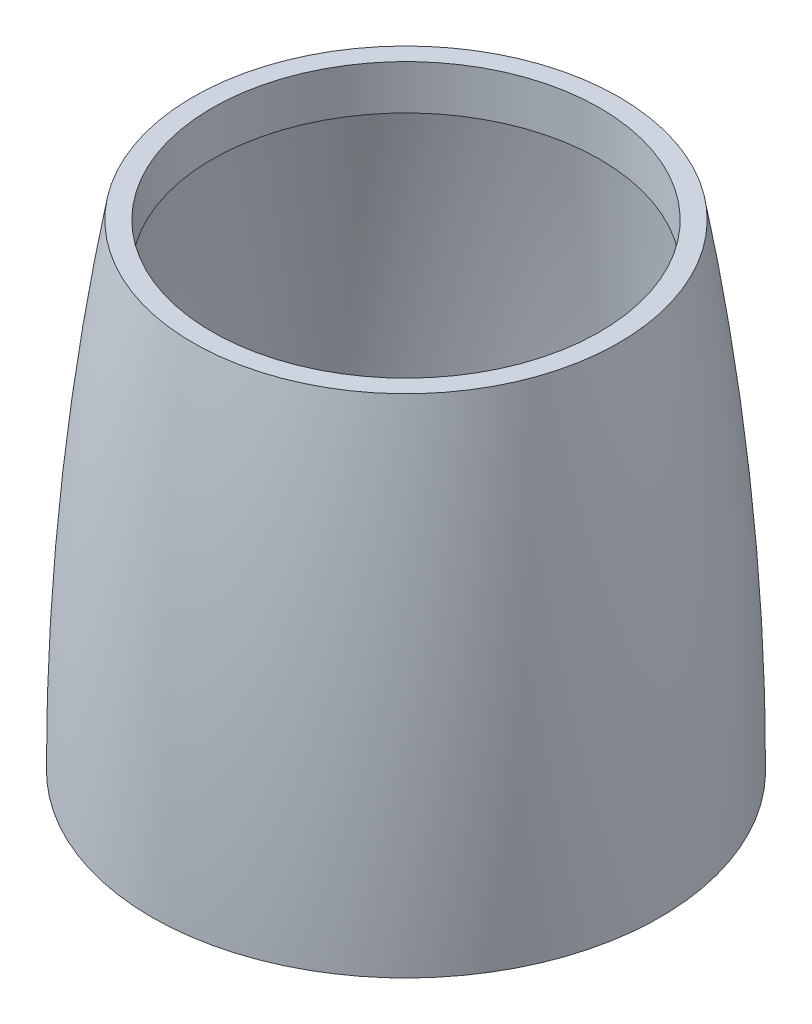
SolidWorks part; units mm, degrees
ref_plane "Front Plane" through (0, 0, 0) normal (0, 0, 1) x (1, 0, 0)
ref_plane "Top Plane" through (0, 0, 0) normal (0, 1, 0) x (1, 0, 0)
ref_plane "Right Plane" through (0, 0, 0) normal (1, 0, 0) x (0, 0, -1)
sketch "Sketch1" plane through (0, 0, 0) normal (0, 0, 1) x (1, 0, 0)
  line L0 (0, 0) -> (0, 46.1851)
  line L2 (0, 0) -> (40, 0)
  line L3 (0, 0) -> (0, 75)
  line L4 (0, 75) -> (40, 75)
  line L5 (40, 0) -> (40, 75)
  line L6 (31.6264, 68) -> (30.5, 68)
  line L7 (31.6264, 68) -> (31.6264, 75)
  line L8 (31.6264, 75) -> (30.5, 75)
  line L9 (30.5, 68) -> (30.5, 75)
  arc A0 (40, 0) -> (33.5, 75) centre (-395.9423, 0) ccw
  arc A1 (37, 0) -> (30.4543, 75) centre (-395.9423, 0) ccw
  arc A2 (37, 0) -> (30.5447, 74.4839) centre (-395.9423, 0) ccw construction
  dimension "D1" = 40
  dimension "D2" = 75
  dimension "D3" = 33.5
  dimension "D5" = 30.5
  dimension "D6" = 7
  dimension "D7" = 0
  dimension "D4" = 3
revolve "Revolve1" add sketch "Sketch1" angle 360 about L3 region at (36.4159, 36.957, 0) region at (31.2401, 72.6833, 0) region at (30.8786, 70.2644, 0)
